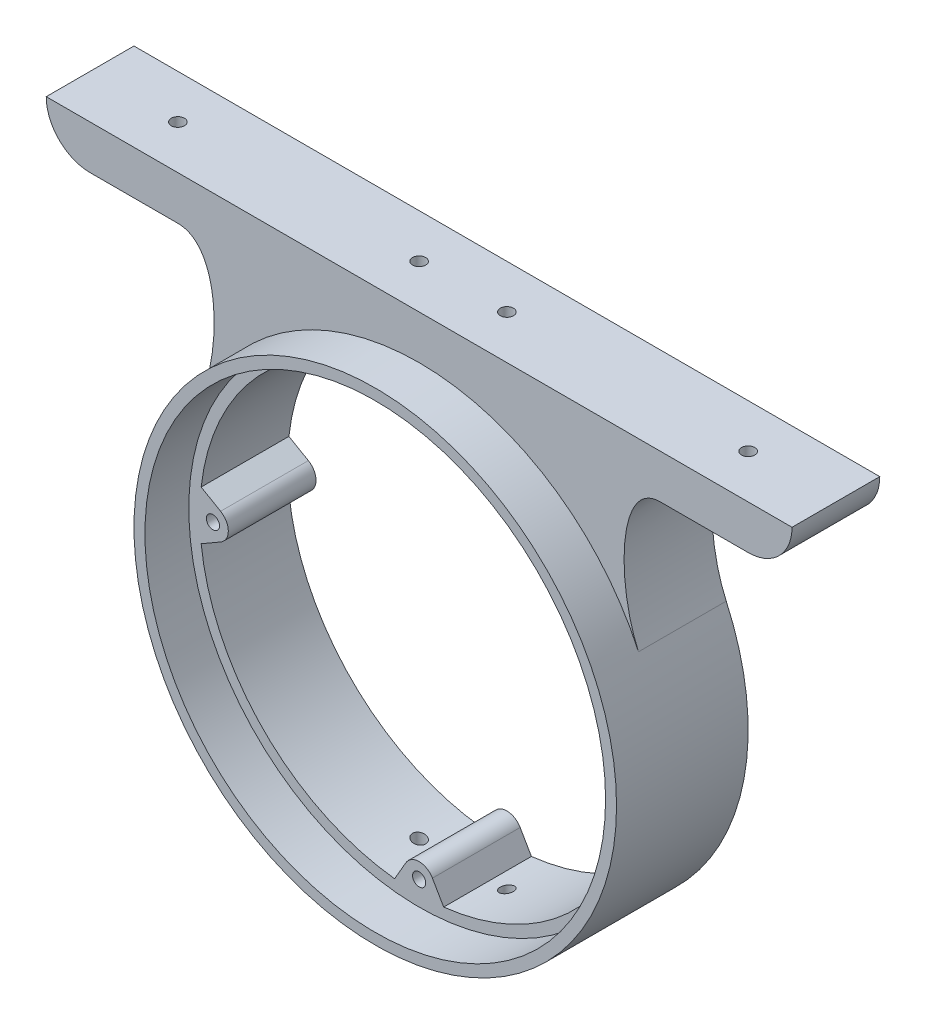
SolidWorks part; units mm, degrees
ref_plane "前视基准面" through (0, 0, 0) normal (0, 0, 1) x (1, 0, 0)
ref_plane "上视基准面" through (0, 0, 0) normal (0, 1, 0) x (1, 0, 0)
ref_plane "右视基准面" through (0, 0, 0) normal (1, 0, 0) x (0, 0, -1)
sketch "草图2" plane through (0, 0, 0) normal (0, 0, 1) x (1, 0, 0)
  line L0 (0, 55) -> (37.8067, 55) construction
  line L1 (-55, 0) -> (-55, 32.093) construction
  line L2 (-45, 109.1596) -> (-45, 87.8343) construction
  line L3 (-55, 55) -> (-85, 55) construction
  line L4 (-85, 55) -> (-85, 65) construction
  line L5 (-75, 55) -> (-55, 55)
  line L6 (0, 104.3034) -> (0, 77.4884) construction
  line L7 (85, 55) -> (85, 65) construction
  line L8 (55, 55) -> (85, 55) construction
  line L9 (75, 55) -> (55, 55)
  line L10 (-85, 65) -> (85, 65)
  line L13 (-50, 22.9129) -> (-45, 33.8238) construction
  line L14 (-45, 33.8238) -> (-45, 55) construction
  line L15 (-45, 55) -> (-55, 55) construction
  line L16 (50, 22.9129) -> (45, 33.8238) construction
  line L17 (45, 33.8238) -> (45, 55) construction
  line L18 (45, 55) -> (55, 55) construction
  circle A1 centre (0, 0) radius 55 construction
  arc A2 (-85, 65) -> (-75, 55) centre (-75, 65) ccw
  arc A3 (85, 65) -> (75, 55) centre (75, 65) cw
  arc A4 (-50, 22.9129) -> (50, 22.9129) centre (0, 0) ccw
  circle A7 centre (0, 0) radius 50
  spline S0 degree 3 poles (-50, 22.9129) (-45, 33.8238) (-45, 55) (-55, 55) knots 0 0 0 0 1 1 1 1
  spline S1 degree 3 poles (50, 22.9129) (45, 33.8238) (45, 55) (55, 55) knots 0 0 0 0 1 1 1 1
  dimension "D1" = 110
  dimension "D2" = 100
  dimension "D3" = 10
  dimension "D5" = 10
  dimension "D4" = 30
  dimension "D8" = 5
extrude "凸台-拉伸1" add sketch "草图2" along normal blind 20
sketch "草图3" plane through (0, 65, 0) normal (0, 1, 0) x (1, 0, 0)
  line L0 (0, 0) -> (0, -20) construction
  line L2 (-85, -10) -> (-55.1419, -10) construction
  line L4 (-85, -20) -> (-85, 0) construction
  circle A0 centre (-65, -10) radius 1.5
  circle A1 centre (-10, -10) radius 1.5
  circle A2 centre (10, -10) radius 1.5
  circle A3 centre (65, -10) radius 1.5
  point P5 (-85, -10)
  dimension "D1" = 3
  dimension "D2" = 10
  dimension "D3" = 55
extrude "切除-拉伸1" cut sketch "草图3" against normal through all
sketch "草图4" plane through (0, 0, 0) normal (0, 0, 1) x (1, 0, 0)
  line L0 (0, 0) -> (-31.4748, 0) construction
  line L1 (-49.6863, 5.5924) -> (-45.25, 3.0311)
  line L2 (-49.6863, -5.5924) -> (-45.25, -3.0311)
  line L3 (0, 0) -> (0, 13.1846) construction
  line L6 (-5.5924, 49.6863) -> (-3.0311, 45.25)
  line L7 (5.5924, 49.6863) -> (3.0311, 45.25)
  line L8 (49.6863, 5.5924) -> (45.25, 3.0311)
  line L9 (49.6863, -5.5924) -> (45.25, -3.0311)
  line L10 (5.5924, -49.6863) -> (3.0311, -45.25)
  line L11 (-5.5924, -49.6863) -> (-3.0311, -45.25)
  circle A0 centre (-47, 0) radius 1.5
  arc A2 (-45.25, 3.0311) -> (-45.25, -3.0311) centre (-47, 0) cw
  arc A3 (-49.6863, 5.5924) -> (-49.6863, -5.5924) centre (0, 0) ccw
  circle A7 centre (0, 0) radius 50 construction
  arc A8 (3.0311, 45.25) -> (-3.0311, 45.25) centre (0, 47) cw
  arc A9 (5.5924, 49.6863) -> (-5.5924, 49.6863) centre (0, 0) ccw
  circle A10 centre (0, 47) radius 1.5
  arc A11 (45.25, -3.0311) -> (45.25, 3.0311) centre (47, 0) cw
  arc A12 (49.6863, -5.5924) -> (49.6863, 5.5924) centre (0, 0) ccw
  circle A13 centre (47, 0) radius 1.5
  arc A14 (-3.0311, -45.25) -> (3.0311, -45.25) centre (0, -47) cw
  arc A15 (-5.5924, -49.6863) -> (5.5924, -49.6863) centre (0, 0) ccw
  circle A16 centre (0, -47) radius 1.5
  point P35 (0, 0)
  dimension "D1" = 30
  dimension "D2" = 2
  dimension "D3" = 3
  dimension "D5" = 4
  dimension "D4" = 47
extrude "凸台-拉伸2" add sketch "草图4" along normal through all
sketch "草图6" plane through (0, 0, 0) normal (0, 1, 0) x (1, 0, 0)
  line L0 (85, 0) -> (-85, 0) construction
  line L1 (-8.4123, -7.25) -> (-11.5877, -7.25)
  line L2 (-11.5877, -7.25) -> (-13.1754, -10)
  line L3 (-13.1754, -10) -> (-11.5877, -12.75)
  line L4 (-11.5877, -12.75) -> (-8.4123, -12.75)
  line L5 (-8.4123, -12.75) -> (-6.8246, -10)
  line L6 (-6.8246, -10) -> (-8.4123, -7.25)
  line L7 (0, 0) -> (0, -20) construction
  line L8 (85, -20) -> (-85, -20) construction
  line L9 (6.8246, -10) -> (8.4123, -7.25)
  line L10 (8.4123, -12.75) -> (6.8246, -10)
  line L11 (11.5877, -12.75) -> (8.4123, -12.75)
  line L12 (13.1754, -10) -> (11.5877, -12.75)
  line L13 (11.5877, -7.25) -> (13.1754, -10)
  line L14 (8.4123, -7.25) -> (11.5877, -7.25)
  circle A0 centre (-10, -10) radius 2.75 construction
  circle A1 centre (10, -10) radius 2.75 construction
  point P11 (-12.3816, -11.375)
  dimension "D1" = 5.5
extrude "切除-拉伸4" cut sketch "草图6" against normal through all from offset 52 offset against normal yes
sketch "草图7" plane through (0, 55, 0) normal (0, -1, 0) x (1, 0, 0)
  line L0 (-75, 20) -> (-55, 20) construction
  line L1 (-63.4123, 12.75) -> (-66.5877, 12.75)
  line L2 (-66.5877, 12.75) -> (-68.1754, 10)
  line L3 (-68.1754, 10) -> (-66.5877, 7.25)
  line L4 (-66.5877, 7.25) -> (-63.4123, 7.25)
  line L5 (-63.4123, 7.25) -> (-61.8246, 10)
  line L6 (-61.8246, 10) -> (-63.4123, 12.75)
  line L7 (0, 0) -> (0, 40.9385) construction
  line L9 (61.8246, 10) -> (63.4123, 12.75)
  line L10 (63.4123, 7.25) -> (61.8246, 10)
  line L11 (66.5877, 7.25) -> (63.4123, 7.25)
  line L12 (68.1754, 10) -> (66.5877, 7.25)
  line L13 (66.5877, 12.75) -> (68.1754, 10)
  line L14 (63.4123, 12.75) -> (66.5877, 12.75)
  circle A0 centre (-65, 10) radius 2.75 construction
  circle A1 centre (65, 10) radius 2.75 construction
  dimension "D1" = 5.5
extrude "切除-拉伸5" cut sketch "草图7" against normal blind 2
sketch "草图9" plane through (0, 0, 20) normal (0, 0, 1) x (1, 0, 0)
  circle A0 centre (0, 0) radius 50
  circle A1 centre (0, 0) radius 55
extrude "凸台-拉伸3" add sketch "草图9" along normal blind 10
sketch "草图10" plane through (0, 0, 30) normal (0, 0, 1) x (1, 0, 0)
  circle A0 centre (0, 0) radius 50
  circle A1 centre (0, 0) radius 52.5
  circle A2 centre (0, 0) radius 50 construction
  dimension "D1" = 2.5
extrude "切除-拉伸6" cut sketch "草图10" against normal blind 10
